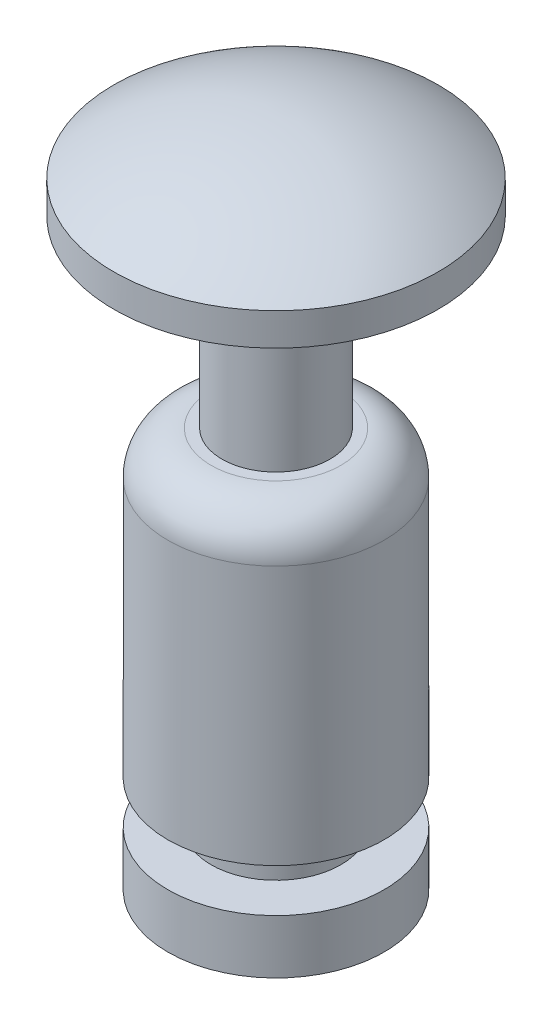
SolidWorks part; units mm, degrees
ref_plane "Front Plane" through (0, 0, 0) normal (0, 0, 1) x (1, 0, 0)
ref_plane "Top Plane" through (0, 0, 0) normal (0, 1, 0) x (1, 0, 0)
ref_plane "Right Plane" through (0, 0, 0) normal (1, 0, 0) x (0, 0, -1)
sketch "Sketch2" plane through (0, 0, 0) normal (0, 1, 0) x (1, 0, 0)
  circle A0 centre (0, 0) radius 1.5
  dimension "D1" = 3
extrude "Boss-Extrude1" add sketch "Sketch2" along normal blind 6.2
sketch "Sketch3" plane through (0, 0, 0) normal (0, 0, 1) x (1, 0, 0)
  line L0 (0, 6.2) -> (0, 0) construction
  line L1 (1.5, 6.2) -> (-1.5, 6.2) construction
  line L2 (1.5, 0) -> (1.5, 6.2) construction
  line L3 (0, 6.2) -> (0, 6.3)
  line L4 (0, 6.3) -> (1.5, 6.3)
  line L5 (1.5, 5.7) -> (1.5, 6.3)
  arc A0 (0, 6.2) -> (1.5, 5.7) centre (0, 3.7) cw
  dimension "D1" = 2.5
  dimension "D2" = 0.1
revolve "Cut-Revolve1" cut sketch "Sketch3" angle 360 about L0
sketch "Sketch5" plane through (0, 0, 0) normal (0, -1, 0) x (1, 0, 0)
  circle A0 centre (0, 0) radius 1
  dimension "D1" = 2
extrude "Cut-Extrude1" cut sketch "Sketch5" against normal blind 5.4 flip side to cut
sketch "Sketch4" plane through (0, 0, 0) normal (0, 0, 1) x (1, 0, 0)
  line L0 (0, 0) -> (0, 6.2) construction
  line L1 (0.6, 0.9) -> (1, 0.9)
  line L2 (0.6, 0.9) -> (0.6, 0.5)
  line L3 (0.6, 0.5) -> (1, 0.5)
  line L4 (1, 0.9) -> (1, 0.5)
  line L5 (-1.5, 0) -> (1.5, 0) construction
  line L7 (1, 0) -> (1, 5.4) construction
  line L8 (-1, 5.4) -> (1, 5.4) construction
  line L9 (0.5, 5.4) -> (1, 5.4)
  line L10 (0.5, 5.4) -> (0.5, 3.7)
  line L11 (0.5, 3.7) -> (1, 3.7)
  line L12 (1, 5.4) -> (1, 3.7)
  dimension "D1" = 1.2
  dimension "D2" = 0.4
  dimension "D3" = 0.9
  dimension "D4" = 1
  dimension "D5" = 2.8
revolve "Cut-Revolve2" cut sketch "Sketch4" angle 360 about L0
fillet "Fillet1" radius 0.4 1 edges at (1, 3.7, 0)
